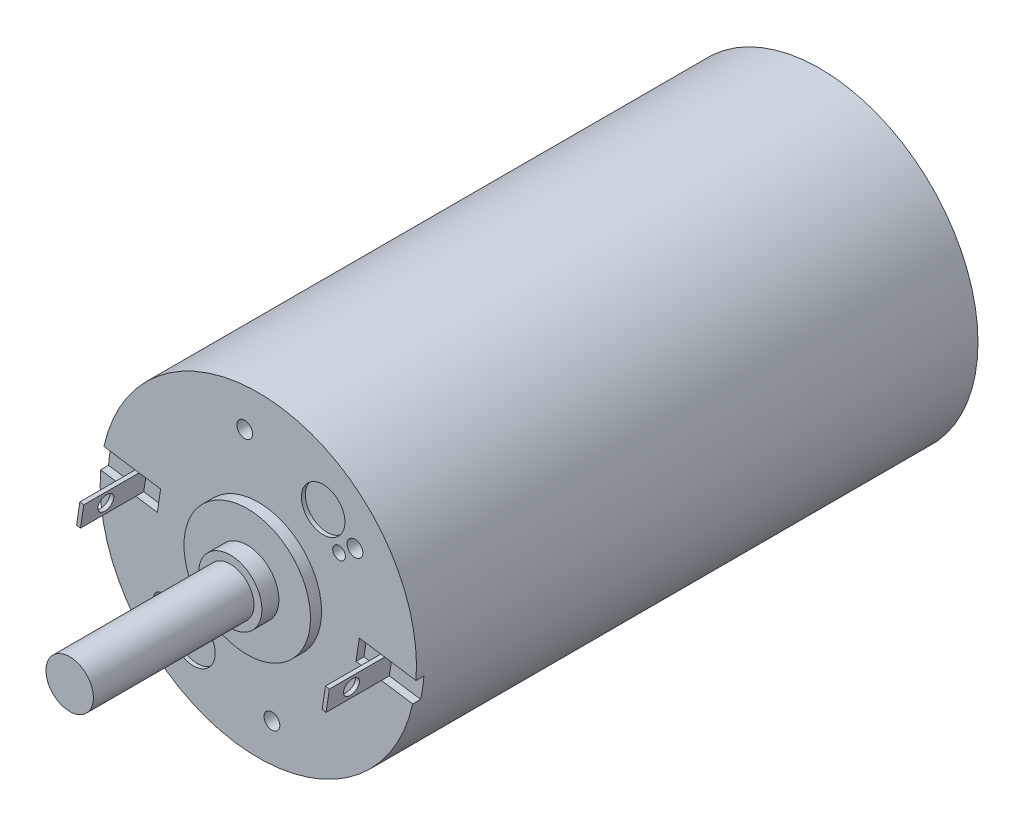
SolidWorks part; units mm, degrees
ref_plane "Front Plane" through (0, 0, 0) normal (0, 0, 1) x (1, 0, 0)
ref_plane "Top Plane" through (0, 0, 0) normal (0, 1, 0) x (1, 0, 0)
ref_plane "Right Plane" through (0, 0, 0) normal (1, 0, 0) x (0, 0, -1)
sketch "Sketch1" plane through (0, 0, 0) normal (0, 0, 1) x (1, 0, 0)
  circle A0 centre (0, 0) radius 20
  dimension "D1" = 40
extrude "Boss-Extrude1" add sketch "Sketch1" along normal blind 71
sketch "Sketch2" plane through (0, 0, 71) normal (0, 0, 1) x (1, 0, 0)
  circle A0 centre (0, 0) radius 8
  dimension "D1" = 16
extrude "Boss-Extrude2" add sketch "Sketch2" along normal blind 1.4
sketch "Sketch3" plane through (0, 0, 72.4) normal (0, 0, 1) x (1, 0, 0)
  circle A0 centre (0, 0) radius 4
  dimension "D1" = 8
extrude "Boss-Extrude3" add sketch "Sketch3" along normal blind 2.15
sketch "Sketch4" plane through (0, 0, 74.55) normal (0, 0, 1) x (1, 0, 0)
  circle A0 centre (0, 0) radius 3
  dimension "D1" = 6
extrude "Boss-Extrude4" add sketch "Sketch4" along normal blind 20.3
sketch "Sketch5" plane through (0, 0, 71) normal (0, 0, 1) x (1, 0, 0)
  line L0 (0, -1000) -> (0, 49000) construction
  line L1 (12.2186, 9.0413) -> (0, 0) construction
  line L2 (0, 0) -> (-20.7009, -15.3178) construction
  line L3 (0, 0) -> (-2.5501, 22.3819) construction
  line L4 (0, 0) -> (2.9246, -25.6693) construction
  line L5 (-1000, 0) -> (49000, 0) construction
  line L6 (0, 0) -> (-49450.7932, 7390.4706) construction
  circle A0 centre (0, 0) radius 15.2 construction
  circle A1 centre (0, 0) radius 12.7 construction
  circle A2 centre (12.2186, 9.0413) radius 1
  circle A4 centre (-12.2186, -9.0413) radius 1
  circle A5 centre (-1.7207, 15.1023) radius 1
  circle A6 centre (1.7207, -15.1023) radius 1
  circle A7 centre (10.209, 7.5542) radius 0.8
  circle A8 centre (-10.209, -7.5542) radius 0.8
  dimension "D1" = 30.4
  dimension "D5" = 2
  dimension "D6" = 25.4
  dimension "D7" = 1.6
  dimension "D2" = 60
  dimension "D3" = 45
  dimension "D4" = 8.5
extrude "Cut-Extrude1" cut sketch "Sketch5" against normal blind 3
sketch "Sketch6" plane through (0, 0, 71) normal (0, 0, 1) x (1, 0, 0)
  line L0 (0, 0) -> (1774.7074, 11874.8443) construction
  line L1 (0, 0) -> (-11874.8443, 1774.7074) construction
  line L2 (-1000, 0) -> (49000, 0) construction
  line L3 (-19.9873, 1.5716) -> (-12.7674, 0.4926)
  line L4 (-19.9873, 1.5716) -> (-19.5734, 4.3408)
  line L5 (-12.7674, 0.4926) -> (-12.3536, 3.2618)
  line L6 (-19.5734, 4.3408) -> (-12.3536, 3.2618)
  line L7 (-19.9873, 1.5716) -> (-12.3536, 3.2618) construction
  line L8 (-12.7674, 0.4926) -> (-19.5734, 4.3408) construction
  line L9 (19.5734, -4.3408) -> (12.3536, -3.2618)
  line L10 (19.5734, -4.3408) -> (19.9873, -1.5716)
  line L11 (12.3536, -3.2618) -> (12.7674, -0.4926)
  line L12 (19.9873, -1.5716) -> (12.7674, -0.4926)
  line L13 (19.5734, -4.3408) -> (12.7674, -0.4926) construction
  line L14 (12.3536, -3.2618) -> (19.9873, -1.5716) construction
  circle A0 centre (0, 0) radius 15.2 construction
  circle A1 centre (0, 0) radius 12.7 construction
  circle A2 centre (0, 0) radius 20 construction
  point P13 (-16.1704, 2.4167)
  point P14 (16.1704, -2.4167)
  point P20 (-22.9854, 10.7092)
  point P25 (0, 0)
  point P26 (-22.1847, 3.3155)
  point P27 (-16.1846, 2.4188)
  point P28 (-16.1778, 2.4178)
  point P29 (-16.2096, 2.4225)
  point P30 (18.1696, -2.7155)
  dimension "D1" = 90
  dimension "D2" = 8.5
  dimension "D3" = 2.8
extrude "Cut-Extrude2" cut sketch "Sketch6" against normal blind 1
sketch "Sketch7" plane through (0, 0, 70) normal (0, 0, 1) x (1, 0, 0)
  line L0 (-12.5605, 1.8772) -> (-49463.3537, 7392.3477) construction
  line L1 (-12.7674, 0.4926) -> (-12.3536, 3.2618) construction
  line L2 (-15.9817, 0.9729) -> (-15.5679, 3.7422)
  line L3 (-15.9817, 0.9729) -> (-15.4872, 0.899)
  line L4 (-15.5679, 3.7422) -> (-15.0734, 3.6683)
  line L5 (-15.4872, 0.899) -> (-15.0734, 3.6683)
  line L6 (-15.9817, 0.9729) -> (-15.0734, 3.6683) construction
  line L7 (-15.5679, 3.7422) -> (-15.4872, 0.899) construction
  line L8 (-12.3536, 3.2618) -> (-19.5249, 4.3336) construction
  line L9 (-19.9387, 1.5643) -> (-12.7674, 0.4926) construction
  line L10 (-12.7674, 0.4926) -> (-12.3536, 3.2618) construction
  line L11 (15.5679, -3.7422) -> (15.9817, -0.9729)
  line L12 (15.5679, -3.7422) -> (15.0734, -3.6683)
  line L13 (15.9817, -0.9729) -> (15.4872, -0.899)
  line L14 (15.0734, -3.6683) -> (15.4872, -0.899)
  line L15 (15.5679, -3.7422) -> (15.4872, -0.899) construction
  line L16 (15.9817, -0.9729) -> (15.0734, -3.6683) construction
  line L17 (19.9387, -1.5643) -> (12.7674, -0.4926) construction
  line L18 (12.3536, -3.2618) -> (19.5249, -4.3336) construction
  line L19 (12.7674, -0.4926) -> (12.3536, -3.2618) construction
  arc A0 (-19.5249, 4.3336) -> (-19.9387, 1.5643) centre (0, 0) ccw construction
  point P4 (-12.5605, 1.8772)
  point P8 (-19.7803, 2.9562)
  point P10 (-15.5275, 2.3206)
  point P21 (15.5275, -2.3206)
  dimension "D1" = 3
  dimension "D2" = 0.5
  dimension "D3" = 0.5
  dimension "D4" = 3
extrude "Boss-Extrude5" add sketch "Sketch7" along normal blind 8
sketch "Sketch8" plane through (0, 0, 71) normal (0, 0, 1) x (1, 0, 0)
  line L0 (0, 0) -> (40192.843, 29741.1393) construction
  line L1 (7.4649, 10.2745) -> (8.9343, 12.2971) construction
  line L2 (-7.4649, -10.2745) -> (-8.9343, -12.2971) construction
  circle A0 centre (0, 0) radius 15.2 construction
  circle A1 centre (0, 0) radius 12.7 construction
  circle A2 centre (8.1996, 11.2858) radius 2.75
  circle A3 centre (-8.1996, -11.2858) radius 2.75
  dimension "D2" = 5.5
  dimension "D1" = 17.5
extrude "Cut-Extrude3" cut sketch "Sketch8" against normal blind 0.5
sketch "Sketch9" plane through (15.7748, -2.3576, 0) normal (0.989, -0.1478, 0) x (0, 0, -1)
  line L0 (-78, -1.4) -> (-78, 1.4) construction
  circle A0 centre (-75, 0) radius 1
  point P4 (-75, 0)
  point P5 (0, 0)
  point P6 (-78, 0)
  dimension "D1" = 2
  dimension "D2" = 3
extrude "Cut-Extrude4" cut sketch "Sketch9" against normal up to next
extrude "Cut-Extrude5" cut sketch "Sketch9<2>" against normal up to next from surface starting at face at (-15.2803, 2.2837, 73)
sketch "Sketch9<2>" plane through (15.7748, -2.3576, 0) normal (0.989, -0.1478, 0) x (0, 0, -1) same geometry as "Sketch9"
sketch "Sketch10" plane through (0, 0, 0) normal (0, 0, -1) x (-1, 0, 0)
  line L0 (0, 0) -> (0, 50000) construction
  line L1 (0, 0) -> (43301.2702, 25000) construction
  line L2 (0, 0) -> (43301.2702, -25000) construction
  circle A3 centre (0, 0) radius 11 construction
  circle A4 centre (0, 11) radius 1.5
  circle A5 centre (9.5263, 5.5) radius 1.5
  circle A6 centre (9.5263, -5.5) radius 1.5
  circle A7 centre (0, -11) radius 1.5
  circle A8 centre (-9.5263, -5.5) radius 1.5
  circle A9 centre (-9.5263, 5.5) radius 1.5
  circle A10 centre (0, 16) radius 1.75
  dimension "D3" = 22
  dimension "D4" = 3
  dimension "D5" = 3.5
  dimension "D1" = 60
  dimension "D2" = 60
  dimension "D6" = 5
extrude "Cut-Extrude6" cut sketch "Sketch10" against normal blind 5
ref_plane "Plane1" through (0, 0, 35.5) normal (0, 0, -1) x (-1, 0, 0)
